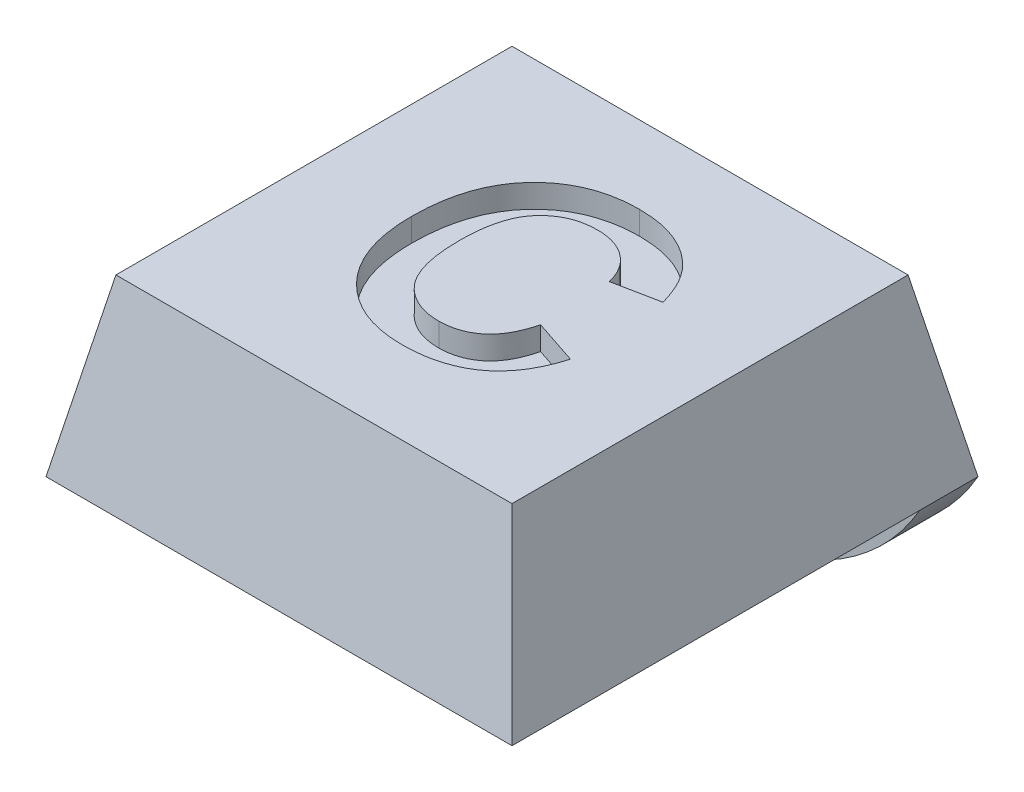
SolidWorks part; units mm, degrees
ref_plane "Front Plane" through (0, 0, 0) normal (0, 0, 1) x (1, 0, 0)
ref_plane "Top Plane" through (0, 0, 0) normal (0, 1, 0) x (1, 0, 0)
ref_plane "Right Plane" through (0, 0, 0) normal (1, 0, 0) x (0, 0, -1)
sketch "Sketch1" plane through (0, 0, 0) normal (0, 1, 0) x (1, 0, 0)
  line L1 (0, 0) -> (8, 0)
  line L2 (0, 0) -> (0, 8)
  line L3 (0, 8) -> (8, 8)
  line L4 (8, 0) -> (8, 8)
  dimension "D1" = 8
  dimension "D2" = 8
extrude "Boss-Extrude1" add sketch "Sketch1" along normal blind 3
sketch "Sketch2" plane through (0, 0, 0) normal (0, 0, 1) x (1, 0, 0)
  line L0 (0, 0) -> (0.6, 3)
  line L1 (0, 3) -> (8, 3) construction
  line L2 (0.6, 3) -> (0, 3)
  line L3 (0, 3) -> (0, 0)
  line L4 (8, 0) -> (7.4, 3)
  line L5 (7.4, 3) -> (8, 3)
  line L6 (8, 3) -> (8, 0)
  dimension "D1" = 0.6
  dimension "D2" = 0.6
extrude "Cut-Extrude1" cut sketch "Sketch2" against normal through all both and the other way through all
sketch "Sketch3" plane through (0, 0, 0) normal (1, 0, 0) x (0, 0, -1)
  line L0 (0, 0) -> (0.6, 3)
  line L1 (8, 3) -> (0, 3) construction
  line L2 (0.6, 3) -> (0, 3)
  line L3 (0, 3) -> (0, 0)
  line L4 (8, 3) -> (7.4, 3)
  line L5 (7.4, 3) -> (8, 0)
  line L6 (8, 3) -> (8, 0)
  dimension "D1" = 0.6
  dimension "D2" = 0.6
extrude "Cut-Extrude2" cut sketch "Sketch3" along normal blind 11
sketch "Sketch4" plane through (0, 0, 0) normal (0, -1, 0) x (1, 0, 0)
  line L0 (8, 0) -> (8, -8) construction
  line L3 (0, 0) -> (8, 0) construction
  circle A0 centre (4, -3.75) radius 1.75
  dimension "D1" = 3.5
  dimension "D2" = 4
  dimension "D3" = 3.75
extrude "Cut-Extrude3" cut sketch "Sketch4" against normal blind 0.4
sketch "Sketch5" plane through (0, 0, 0) normal (0, -1, 0) x (1, 0, 0)
  line L0 (8, 0) -> (8, -8) construction
  line L1 (0, -8) -> (8, -8)
  line L2 (0, -8) -> (0, -7)
  line L3 (0, -7) -> (8, -7)
  line L4 (8, -8) -> (8, -7)
  dimension "D1" = 1
extrude "Boss-Extrude2" add sketch "Sketch5" along normal blind 2
fillet "Fillet1" radius 4 2 edges at (8, -2, -7.5) (0, -2, -7.5)
sketch "Sketch6" plane through (0, 3, 0) normal (0, 1, 0) x (1, 0, 0)
  text T0 "C" font "Arial" height 4
extrude "Cut-Extrude4" cut sketch "Sketch6" against normal blind 0.4
